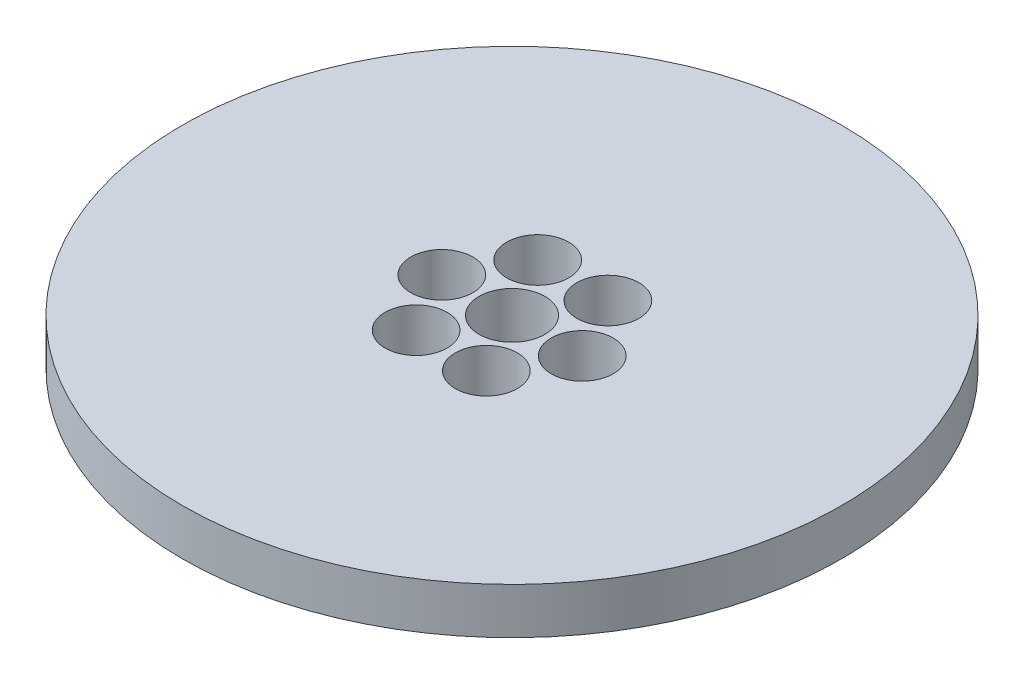
SolidWorks part; units mm, degrees
ref_plane "Front Plane" through (0, 0, 0) normal (0, 0, 1) x (1, 0, 0)
ref_plane "Top Plane" through (0, 0, 0) normal (0, 1, 0) x (1, 0, 0)
ref_plane "Right Plane" through (0, 0, 0) normal (1, 0, 0) x (0, 0, -1)
sketch "Sketch1" plane through (0, 0, 0) normal (0, 1, 0) x (1, 0, 0)
  circle A0 centre (0, 0) radius 50
  dimension "FLANGE_OD" = 100
extrude "Boss-Extrude1" add sketch "Sketch1" along normal blind 7
sketch "Sketch2" plane through (0, 0, 0) normal (0, 1, 0) x (1, 0, 0)
  circle A0 centre (0, 0) radius 5
  dimension "BORE_D" = 10
extrude "Cut-Extrude1" cut sketch "Sketch2" along normal through all
sketch "Sketch3" plane through (0, 7, 0) normal (0, 1, 0) x (1, 0, 0)
  circle A0 centre (0, 0) radius 10.6506 construction
  circle A1 centre (-10.6506, 0) radius 4.7073
  dimension "BOLT_D" = 9.4146
  dimension "BOLT_PCD" = 21.3013
extrude "Cut-Extrude2" cut sketch "Sketch3" against normal blind 6.7313
pattern_circular "CirPattern1" count 6 over 360 about axis through (0, 0, 0) along (0, 1, 0) of "Cut-Extrude2"
